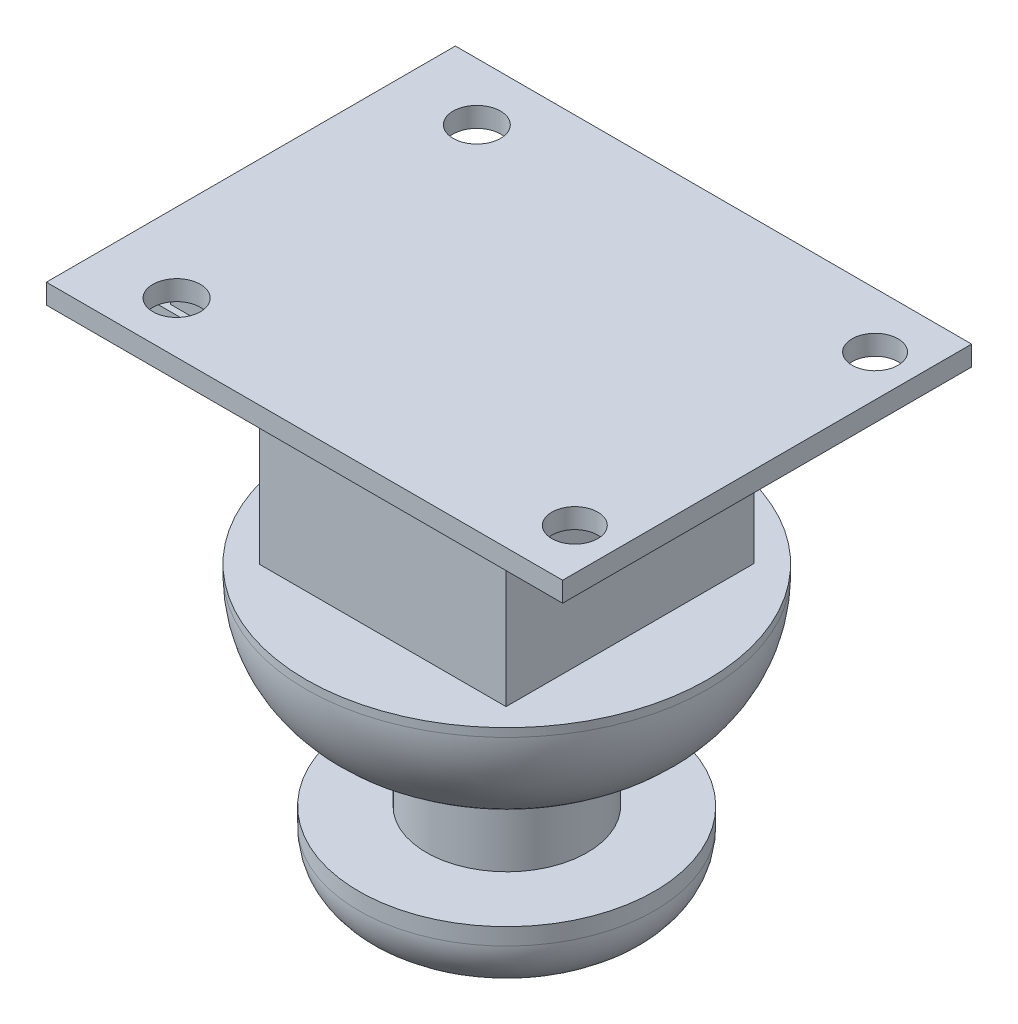
SolidWorks part; units mm, degrees
ref_plane "Спереди" through (0, 0, 0) normal (0, 0, 1) x (1, 0, 0)
ref_plane "Сверху" through (0, 0, 0) normal (0, 1, 0) x (1, 0, 0)
ref_plane "Справа" through (0, 0, 0) normal (1, 0, 0) x (0, 0, -1)
sketch "Эскиз1" plane through (0, 0, 0) normal (0, 1, 0) x (1, 0, 0)
  line L0 (33.7, 0) -> (30.9983, 0) construction
  line L1 (33.7, 26.7) -> (0, 26.7)
  line L2 (33.7, 26.7) -> (33.7, 0)
  line L3 (33.7, 0) -> (0, 0)
  line L4 (0, 26.7) -> (0, 0)
  line L5 (30.9983, 0) -> (30.9983, 3.4986) construction
  line L6 (30.9983, 3.4986) -> (33.7, 3.4986) construction
  line L7 (33.7, 26.7) -> (30.9983, 26.7) construction
  line L8 (30.9983, 26.7) -> (30.9983, 23.0985) construction
  line L9 (30.9983, 23.0985) -> (33.7, 23.0985) construction
  line L10 (0, 0) -> (5.1505, 0) construction
  line L11 (5.1505, 0) -> (5.1505, 3.3527) construction
  line L12 (5.1505, 3.3527) -> (0, 3.3527) construction
  line L13 (0, 26.7) -> (5.1505, 26.7) construction
  line L14 (5.1505, 26.7) -> (5.1505, 22.95) construction
  line L15 (5.1505, 22.95) -> (0, 22.95) construction
  circle A0 centre (30.9983, 3.4986) radius 1.5002
  circle A1 centre (30.9983, 23.0985) radius 1.5
  circle A2 centre (5.1505, 3.3527) radius 1.5523
  circle A3 centre (5.1505, 22.95) radius 1.5465
  point P12 (30.9983, 21.5985)
  point P13 (30.9983, 4.9988)
  point P14 (30.9983, 1.9985)
  point P15 (30.9983, 24.5985)
  point P16 (32.4984, 3.4986)
  point P25 (5.1505, 21.4035)
  point P26 (5.1505, 24.4965)
extrude "Бобышка-Вытянуть1" add sketch "Эскиз1" along normal blind 1.3
sketch "Эскиз2" plane through (0, 0, 0) normal (0, -1, 0) x (1, 0, 0)
  line L0 (0, 0) -> (0, -6.6956) construction
  line L1 (0, -26.7) -> (0, 0) construction
  line L2 (0, -6.6956) -> (1.3986, -6.6956) construction
  line L4 (1.3986, -6.6956) -> (3.9964, -6.6956)
  line L5 (1.3986, -6.6956) -> (1.3986, -19.292)
  line L6 (1.3986, -19.292) -> (3.9964, -19.292)
  line L7 (3.9964, -6.6956) -> (3.9964, -19.292)
extrude "Бобышка-Вытянуть3" add sketch "Эскиз2" along normal blind 2.6
sketch "Эскиз3" plane through (0, -2.6, 0) normal (0, -1, 0) x (1, 0, 0)
  line L0 (1.3986, -19.292) -> (1.3986, -18.491) construction
  line L1 (1.3986, -6.6956) -> (1.3986, -19.292) construction
  line L2 (1.3986, -18.491) -> (2.2964, -18.491) construction
  line L3 (3.0979, -18.491) -> (3.9964, -18.491) construction
  line L4 (2.2964, -18.491) -> (3.0979, -18.491)
  line L5 (2.2964, -18.491) -> (2.2964, -17.6906)
  line L6 (2.2964, -17.6906) -> (3.0979, -17.6906)
  line L7 (3.0979, -18.491) -> (3.0979, -17.6906)
  line L8 (3.9964, -19.292) -> (3.9964, -6.6956) construction
  line L9 (2.2964, -17.6906) -> (2.2964, -16.0942) construction
  line L10 (2.2964, -15.2921) -> (2.2964, -13.4902) construction
  line L11 (2.2964, -16.0942) -> (3.0979, -16.0942)
  line L12 (2.2964, -16.0942) -> (2.2964, -15.2921)
  line L13 (2.2964, -15.2921) -> (3.0979, -15.2921)
  line L14 (3.0979, -16.0942) -> (3.0979, -15.2921)
  line L15 (2.2964, -12.6917) -> (2.2964, -11.0905) construction
  line L16 (2.2964, -13.4902) -> (3.0979, -13.4902)
  line L17 (2.2964, -13.4902) -> (2.2964, -12.6917)
  line L18 (2.2964, -12.6917) -> (3.0979, -12.6917)
  line L19 (3.0979, -13.4902) -> (3.0979, -12.6917)
  line L20 (2.2964, -10.2875) -> (2.2964, -8.4842) construction
  line L21 (2.2964, -11.0905) -> (3.0979, -11.0905)
  line L22 (2.2964, -11.0905) -> (2.2964, -10.2875)
  line L23 (2.2964, -10.2875) -> (3.0979, -10.2875)
  line L24 (3.0979, -11.0905) -> (3.0979, -10.2875)
  line L25 (2.2964, -7.6799) -> (2.2964, -6.6956) construction
  line L26 (2.2964, -8.4842) -> (3.0979, -8.4842)
  line L27 (2.2964, -8.4842) -> (2.2964, -7.6799)
  line L28 (2.2964, -7.6799) -> (3.0979, -7.6799)
  line L29 (3.0979, -8.4842) -> (3.0979, -7.6799)
  line L30 (3.9964, -6.6956) -> (1.3986, -6.6956) construction
sketch "Эскиз4" plane through (0, 0, 0) normal (0, 0, 1) x (1, 0, 0)
  line L0 (2.6971, -2.6) -> (2.6971, -3.4)
  line L1 (1.6971, -4.4) -> (-4.903, -4.4)
  line L2 (2.2964, -2.6) -> (3.0979, -2.6) construction
  arc A0 (2.6971, -3.4) -> (1.6971, -4.4) centre (1.6971, -3.4) cw
  dimension "D1" = 1
ref_plane "Плоскость3" through (2.6971, -2.6, 0) normal (0, -1, 0) x (-1, 0, 0)
sweep "По траектории3" add profiles "Эскиз3" path "Эскиз4"
sketch "Эскиз6" plane through (0, 0, 0) normal (0, -1, 0) x (1, 0, 0)
  line L0 (0, -26.7) -> (9.2005, -26.7) construction
  line L1 (33.7, -26.7) -> (0, -26.7) construction
  line L2 (9.2005, -26.7) -> (9.2005, -20.905) construction
  line L3 (9.2005, -20.905) -> (25.3022, -20.905) construction
  line L4 (25.3022, -20.905) -> (25.3022, -4.7062) construction
  line L6 (25.3022, -20.905) -> (9.2005, -20.905)
  line L7 (25.3022, -20.905) -> (25.3022, -4.7062)
  line L8 (25.3022, -4.7062) -> (9.2005, -4.7062)
  line L9 (9.2005, -20.905) -> (9.2005, -4.7062)
extrude "Бобышка-Вытянуть4" add sketch "Эскиз6" along normal blind 12.4
sketch "Эскиз7" plane through (0, -12.4, 0) normal (0, -1, 0) x (1, 0, 0)
  line L0 (9.2005, -4.7062) -> (25.3022, -20.905) construction
  line L1 (25.3022, -20.905) -> (25.3022, -4.7062) construction
  line L2 (25.3022, -4.7062) -> (17.2514, -12.8056) construction
  circle A0 centre (17.2514, -12.8056) radius 13.1019
extrude "Бобышка-Вытянуть5" add sketch "Эскиз7" along normal blind 8.4
fillet "Скругление1" radius 7.85 1 edges at (17.2514, -20.8, -25.9075) type face fillet first side face at (17.2514, -20.8, -25.9075) second side face at (17.2514, -20.8, -25.9075)
sketch "Эскиз9" plane through (0, -20.8, 0) normal (0, -1, 0) x (1, 0, 0)
  line L0 (15.3232, -7.9204) -> (19.1796, -17.6908) construction
  circle A0 centre (17.2514, -12.8056) radius 5.2519 construction
  arc A1 (19.1796, -17.6908) -> (22.1365, -10.8774) centre (17.2514, -12.8056) ccw construction
  circle A2 centre (17.2514, -12.8056) radius 5.2519
extrude "Бобышка-Вытянуть6" add sketch "Эскиз9" along normal blind 5.3
sketch "Эскиз12" plane through (0, -26.1, 0) normal (0, -1, 0) x (1, 0, 0)
  line L0 (15.4657, -7.8666) -> (19.007, -17.7554) construction
  circle A0 centre (17.2514, -12.8056) radius 5.2519 construction
  circle A1 centre (17.2363, -12.811) radius 9.6512
extrude "Бобышка-Вытянуть8" add sketch "Эскиз12" along normal blind 4.6
fillet "Скругление2" radius 3.5 1 edges at (17.2363, -30.7, -22.4621) type face fillet first side face at (17.2363, -30.7, -22.4621) second side face at (17.2363, -30.7, -22.4621)
